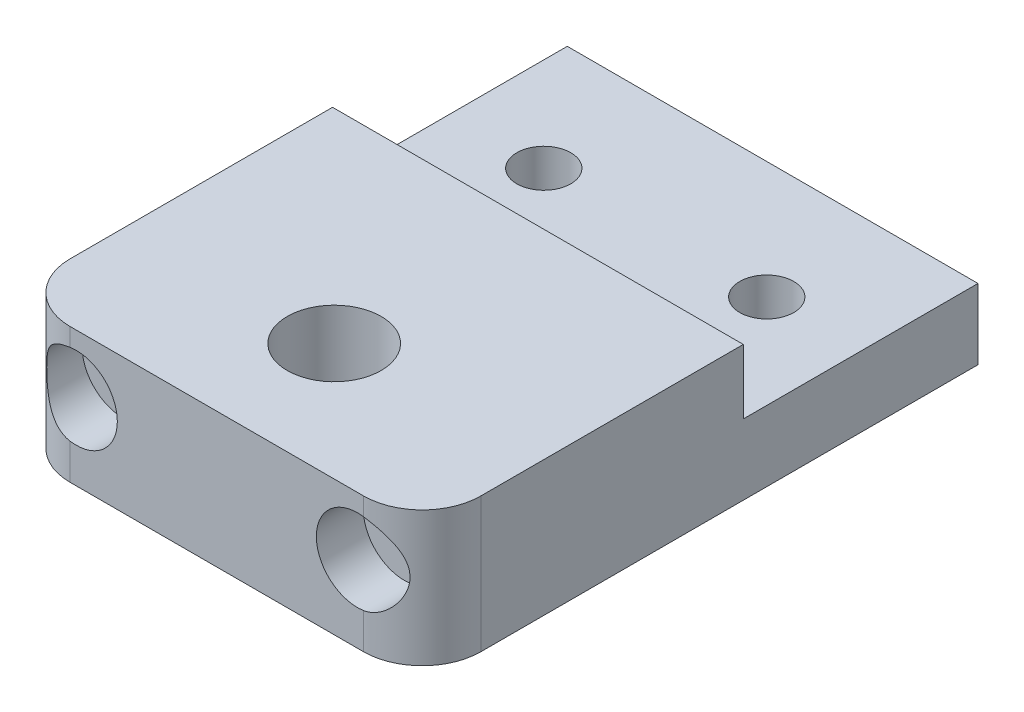
SolidWorks part; units mm, degrees
ref_plane "Front Plane" through (0, 0, 0) normal (0, 0, 1) x (1, 0, 0)
ref_plane "Top Plane" through (0, 0, 0) normal (0, 1, 0) x (1, 0, 0)
ref_plane "Right Plane" through (0, 0, 0) normal (1, 0, 0) x (0, 0, -1)
sketch "Sketch1" plane through (0, 0, 0) normal (0, 1, 0) x (1, 0, 0)
  line L1 (-17.5, 26.3958) -> (17.5, 26.3958)
  line L2 (-17.5, 26.3958) -> (-17.5, -0.9642)
  line L3 (-17.5, -0.9642) -> (17.5, -0.9642)
  line L4 (17.5, 26.3958) -> (17.5, -0.9642)
  line L5 (-17.5, 26.3958) -> (17.5, -0.9642) construction
  line L6 (-17.5, -0.9642) -> (17.5, 26.3958) construction
  line L9 (0, 12.7158) -> (0, 9.0358) construction
  circle A0 centre (0, 9.0358) radius 4
  dimension "D1" = 8
  dimension "D2" = 35
  dimension "D3" = 10
extrude "Boss-Extrude1" add sketch "Sketch1" along normal blind 5.5
sketch "Sketch2" plane through (0, 5.5, 0) normal (0, 1, 0) x (1, 0, 0)
  line L0 (17.5, 26.3958) -> (-17.5, 26.3958) construction
  line L1 (-17.5, -0.9642) -> (17.5, -0.9642)
  line L2 (-17.5, -0.9642) -> (-17.5, 46.3958)
  line L3 (-17.5, 46.3958) -> (17.5, 46.3958)
  line L4 (17.5, -0.9642) -> (17.5, 46.3958)
  line L5 (-17.5, 36.3958) -> (17.5, 36.3958) construction
  line L6 (17.5, -0.9642) -> (17.5, 26.3958) construction
  circle A0 centre (-9.5, 36.3958) radius 2.3
  circle A1 centre (9.5, 36.3958) radius 2.3
  circle M11 centre (0, 9.0358) radius 4
  dimension "D3" = 4.6
  dimension "D4" = 4.6
  dimension "D1" = 20
  dimension "D2" = 10
  dimension "D5" = 8
  dimension "D6" = 8
extrude "Boss-Extrude2" add sketch "Sketch2" against normal blind 6 from surface contours A0 L5 | L5 A0 | A1 L5 | L5 A1 | M11 | L3 L4 L1 L2 region at (-9.5, 5.5, -37.372) region at (-9.5, 5.5, -35.4197) region at (9.5, 5.5, -35.4197) region at (9.5, 5.5, -37.372) region at (0, 5.5, -9.0358) starting at face at (0, 0, -12.7158)
fillet "Fillet1" radius 5 2 edges at (17.5, -0.25, 0.9642) (-17.5, -0.25, 0.9642)
sketch "Sketch3" plane through (0, -6, 0) normal (0, -1, 0) x (-1, 0, 0)
  line L0 (-17.5, 9.0358) -> (17.5, 9.0358) construction
  point P6 (0, 9.0358)
ref_plane "Plane1" through (0, 0, -9.0358) normal (0, 0, -1) x (-1, 0, 0)
sketch "Sketch4" plane through (0, 0, -9.0358) normal (0, 0, -1) x (-1, 0, 0)
  line L0 (0, 5.5) -> (0, 0) construction
  line L1 (-11.9802, 0.5) -> (11.9802, 0.5) construction
  line L2 (12.5, 5.5) -> (-12.5, 5.5) construction
  line L4 (-17.5, 5.5) -> (17.5, 5.5) construction
  circle A0 centre (-11.9802, 0.5) radius 3.5
  circle A1 centre (11.9802, 0.5) radius 3.5
  circle A2 centre (-11.9802, 0.5) radius 1.4
  circle A3 centre (11.9802, 0.5) radius 1.4
  point P10 (0, -6)
  point P11 (0, 0.5)
  point P12 (0, 0)
  point P13 (0, -3.6721)
  point P14 (0, 6.6715)
  point P17 (0.5086, 1.7658)
  point P18 (0, 0)
  dimension "D1" = 7
  dimension "D2" = 2.8
  dimension "D3" = 5
extrude "Cut-Extrude1" cut sketch "Sketch4" along normal blind 15 and the other way through all contours A2 | A3 region at (11.9802, 0.5, -9.0358) region at (-11.9802, 0.5, -9.0358)
extrude "Cut-Extrude2" cut sketch "Sketch4<3>" against normal blind 15 from offset 6 offset against normal yes
sketch "Sketch4<3>" plane through (0, 0, -9.0358) normal (0, 0, -1) x (-1, 0, 0) same geometry as "Sketch4"
